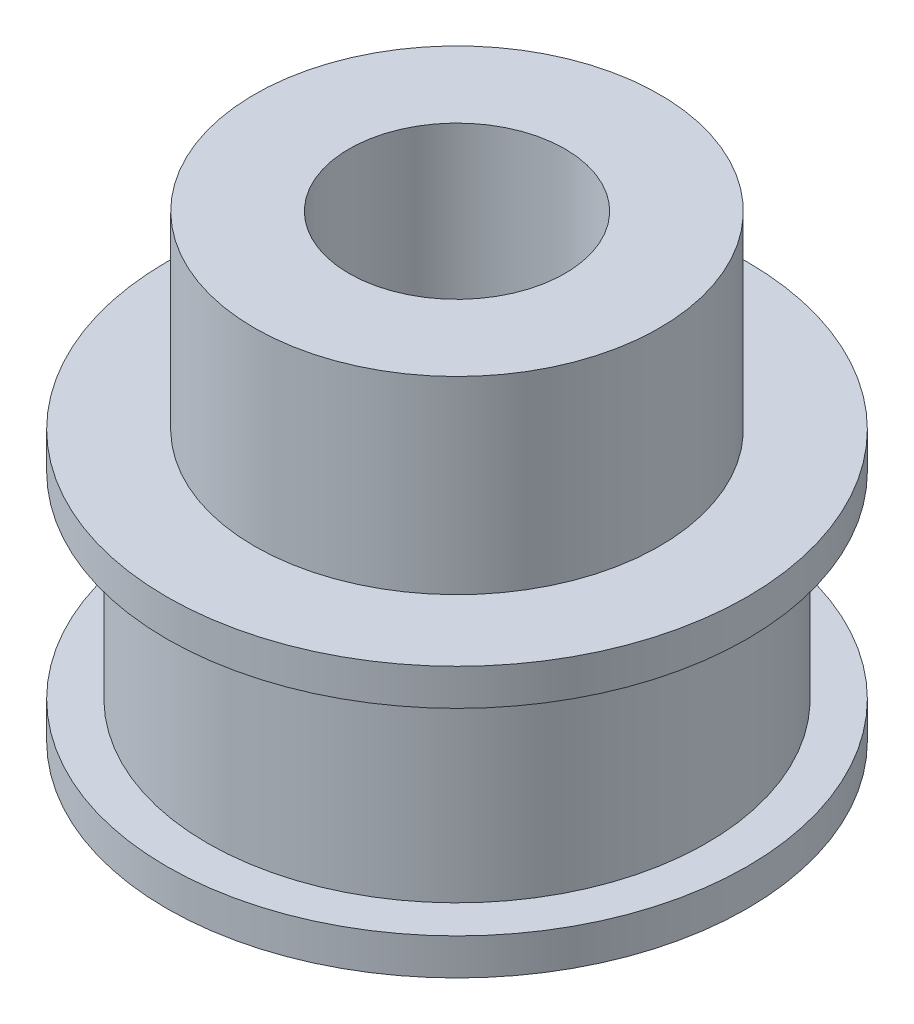
SolidWorks part; units mm, degrees
ref_plane "前视基准面" through (0, 0, 0) normal (0, 0, 1) x (1, 0, 0)
ref_plane "上视基准面" through (0, 0, 0) normal (0, 1, 0) x (1, 0, 0)
ref_plane "右视基准面" through (0, 0, 0) normal (1, 0, 0) x (0, 0, -1)
other "Configuration Table"
sketch "草图1" plane through (0, 0, 0) normal (0, 1, 0) x (1, 0, 0)
  circle A0 centre (0, 0) radius 10.75
  dimension "D1" = 21.5
extrude "凸台-拉伸1" add sketch "草图1" along normal blind 1.35 contours A0 region at (0, 0, 0)
sketch "草图4" plane through (0, 1.35, 0) normal (0, 1, 0) x (1, 0, 0)
  circle A0 centre (0, 0) radius 9.25
  dimension "D1" = 18.5
extrude "凸台-拉伸3" add sketch "草图4" along normal blind 7.3
extrude "凸台-拉伸4" add sketch "草图1<4>" along normal blind 1.35 from surface starting at face at (0, 8.65, 9.25)
sketch "草图1<4>" plane through (0, 0, 0) normal (0, 1, 0) x (1, 0, 0) same geometry as "草图1"
sketch "草图6" plane through (0, 10, 0) normal (0, 1, 0) x (1, 0, 0)
  circle A0 centre (0, 0) radius 7.5
  dimension "D1" = 15
extrude "凸台-拉伸5" add sketch "草图6" along normal blind 7
sketch "草图5" plane through (0, 0, 0) normal (0, -1, 0) x (1, 0, 0)
  circle A0 centre (0, 0) radius 4
  dimension "D1" = 8
extrude "切除-拉伸1" cut sketch "草图5" against normal through all
